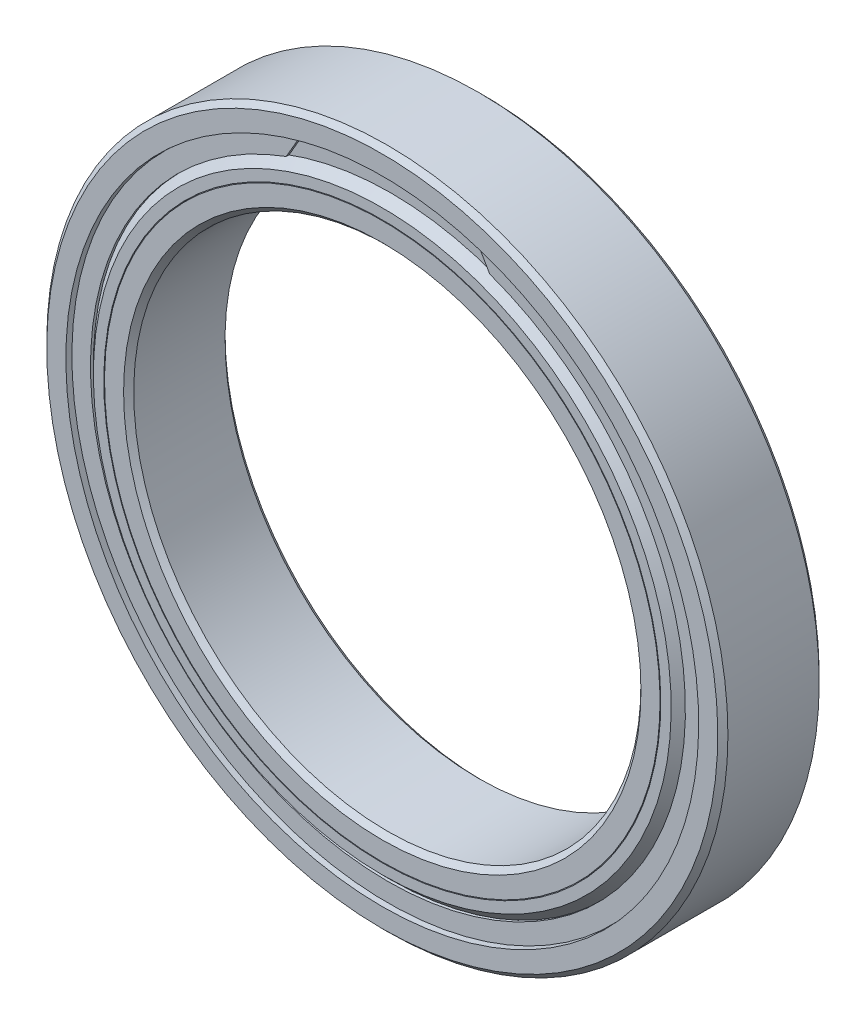
SolidWorks part; units mm, degrees
ref_plane "Front Plane" through (0, 0, 0) normal (0, 0, 1) x (1, 0, 0)
ref_plane "Top Plane" through (0, 0, 0) normal (0, 1, 0) x (1, 0, 0)
ref_plane "Right Plane" through (0, 0, 0) normal (1, 0, 0) x (0, 0, -1)
sketch "Sketch1" plane through (0, 0, 0) normal (0, 0, 1) x (1, 0, 0)
  circle A0 centre (0, 0) radius 23.5
  circle A1 centre (0, 0) radius 17.5
  dimension "OD" = 47
  dimension "ID" = 35
  dimension "For Shaft Diameter" = 35
sketch "Sketch8" plane through (0, 0, 0) normal (1, 0, 0) x (0, 0, -1)
  line L1 (-3.5, 23.5) -> (3.5, 23.5)
  line L2 (-3.5, 23.5) -> (-3.5, -23.5)
  line L3 (-3.5, -23.5) -> (3.5, -23.5)
  line L4 (3.5, 23.5) -> (3.5, -23.5)
  line L5 (-3.5, 23.5) -> (3.5, -23.5) construction
  line L6 (-3.5, -23.5) -> (3.5, 23.5) construction
  point P0 (0, 0)
  point P6 (0, -23.5)
  dimension "Width" = 7
sketch "Sketch5" plane through (0, 0, 0) normal (1, 0, 0) x (0, 0, -1)
  line L0 (-3.5, 0) -> (3.5, 0) construction
  line L1 (0, 23.5) -> (0, -23.5) construction
  line L2 (3.15, 23.5) -> (-3.15, 23.5)
  line L3 (-3.15, 23.5) -> (-3.5, 23.15)
  line L4 (-3.5, 23.15) -> (-3.5, 21.8333)
  line L5 (-3.5, 21.8333) -> (-1.5556, 21.8333)
  line L6 (3.5, 21.8333) -> (1.5556, 21.8333)
  line L7 (3.5, 23.15) -> (3.5, 21.8333)
  line L8 (3.15, 23.5) -> (3.5, 23.15)
  line L9 (0, 23.5) -> (0, 20.5) construction
  line L10 (0, 20.5) -> (0, 17.5) construction
  line L11 (-1.9373, 21.1667) -> (-3.5, 21.1667) construction
  line L12 (2.5281, 20.5254) -> (2.9091, 20.5254)
  line L13 (-2.5281, 20.5254) -> (-2.9091, 20.5254)
  line L14 (-2.5281, 20.5254) -> (-2.5281, 21.8079)
  line L15 (-2.5281, 21.8079) -> (-2.9091, 21.8079)
  line L16 (-2.9091, 20.5254) -> (-2.9091, 21.8079)
  line L17 (-2.5281, 20.5254) -> (-2.9091, 21.8079) construction
  line L18 (-2.5281, 21.8079) -> (-2.9091, 20.5254) construction
  line L19 (2.9091, 20.5254) -> (2.9091, 21.8079)
  line L20 (2.5281, 21.8079) -> (2.9091, 21.8079)
  line L21 (2.5281, 20.5254) -> (2.5281, 21.8079)
  line L22 (0, 23.5) -> (0, -23.5) construction
  line L23 (3.5, 0) -> (3.5, 23.5) construction
  line L24 (3.5, 23.5) -> (3.15, 23.5) construction
  line L25 (-3.5, 0) -> (-3.5, 23.5) construction
  line L26 (-3.5, 23.5) -> (-3.15, 23.5) construction
  line L27 (3.5, 0) -> (3.5, -23.5) construction
  line L28 (-3.5, 0) -> (-3.5, -23.5) construction
  line L29 (-3.5, -23.5) -> (3.5, -23.5) construction
  line L30 (-2.0488, 20.5) -> (-2.0488, 21.8333) construction
  line L31 (-2.0488, 21.1667) -> (-2.0488, 20.5) construction
  line L32 (-2.0488, 20.8333) -> (-2.0488, 21.1667) construction
  arc A0 (-1.5556, 21.8333) -> (1.5556, 21.8333) centre (0, 20.5) cw
  circle A1 centre (0, 20.5) radius 2.0488 construction
  point P14 (0, 17.5)
  point P15 (-2.7186, 21.1667)
  point P36 (-2.0488, 21.1667)
  dimension "D1" = 45
  dimension "D2" = 0.35
  dimension "D3" = 3.1111
  dimension "D4" = 1.3333
  dimension "D5" = 0.381
  dimension "D6" = 0.0254
revolve "Revolve1" add sketch "Sketch5" angle 360 about L0
sketch "Sketch3" plane through (0, 0, 0) normal (1, 0, 0) x (0, 0, -1)
  line L0 (-3.5, 19.1667) -> (-1.5556, 19.1667)
  line L1 (0, 23.5) -> (0, -23.5) construction
  line L2 (-3.5, 23.15) -> (-3.5, 21.8333) construction
  line L3 (-3.5, 19.1667) -> (-3.5, 17.85)
  line L4 (-3.15, 23.5) -> (-3.5, 23.15) construction
  line L5 (-3.5, 17.85) -> (-3.15, 17.5)
  line L6 (-3.15, 17.5) -> (3.15, 17.5)
  line L7 (3.15, 23.5) -> (3.15, -23.5) construction
  line L8 (3.15, 17.5) -> (3.5, 17.85)
  line L9 (3.5, -23.15) -> (3.5, 23.15) construction
  line L10 (3.5, 17.85) -> (3.5, 19.1667)
  line L11 (3.5, 19.1667) -> (1.5556, 19.1667)
  line L13 (3.15, 23.5) -> (3.5, 23.15) construction
  arc A0 (1.5556, 21.8333) -> (-1.5556, 21.8333) centre (0, 20.5) ccw construction
  arc A1 (1.5556, 19.1667) -> (-1.5556, 19.1667) centre (0, 20.5) cw
revolve "Revolve3" add sketch "Sketch3" angle 360 about L0
sketch "Sketch9" plane through (0, 0, 0) normal (1, 0, 0) x (0, 0, -1)
  line L0 (-2.9091, 20.5254) -> (-3.5, 19.9345)
  line L1 (-3.5, 0) -> (-3.5, 23.5) construction
  line L2 (-3.5, 19.9345) -> (-3.5, 19.2167)
  line L3 (-3.5, 19.2167) -> (-2.5281, 19.2167)
  line L4 (-2.5281, 19.2167) -> (-2.5281, 20.5254)
  line L5 (-3.5, 19.1667) -> (-1.5556, 19.1667) construction
  line L6 (-2.9091, 20.5254) -> (-2.5281, 20.5254)
  line L7 (0, 23.5) -> (0, -23.5) construction
  line L8 (0, 23.5) -> (0, -23.5) construction
  line L9 (2.9091, 20.5254) -> (2.5281, 20.5254)
  line L10 (2.5281, 19.2167) -> (2.5281, 20.5254)
  line L11 (3.5, 19.2167) -> (2.5281, 19.2167)
  line L12 (3.5, 19.9345) -> (3.5, 19.2167)
  line L13 (2.9091, 20.5254) -> (3.5, 19.9345)
  dimension "D1" = 0.05
  dimension "D2" = 45
revolve "Revolve5" add sketch "Sketch9" angle 360 about L0
sketch "Sketch10" plane through (0, 0, 2.9091) normal (0, 0, 1) x (1, 0, 0)
  line L0 (0, 0) -> (-7.4588, 20.4928) construction
  line L1 (-7.4588, 20.4928) -> (7.4588, 20.4928) construction
  line L2 (7.4588, 20.4928) -> (0, 0) construction
  line L3 (-7.0201, 19.2876) -> (-6.061, 20.9487)
  line L4 (0, 0) -> (0, 23.5) construction
  line L5 (0, 0) -> (0, 23.5) construction
  line L6 (7.0201, 19.2876) -> (6.061, 20.9487)
  circle A0 centre (0, 0) radius 20.5254 construction
  circle A1 centre (0, 0) radius 21.8079
  circle A2 centre (0, 0) radius 21.8079 construction
  circle A3 centre (0, 0) radius 20.5254 construction
  circle A4 centre (0, 0) radius 21.8079 construction
  arc A7 (-7.0201, 19.2876) -> (7.0201, 19.2876) centre (0, 0) ccw
  arc A8 (6.061, 20.9487) -> (-6.061, 20.9487) centre (0, 0) cw
  dimension "D2" = 40
  dimension "D3" = 30
  dimension "D1" = 0
extrude "Boss-Extrude1" add sketch "Sketch10" along normal blind 0.2 separate body
mirror "Mirror2" about plane through (0, 0, 0) normal (0, 0, 1) of bodies 149
sketch "Sketch4" plane through (0, 0, 0) normal (1, 0, 0) x (0, 0, -1)
  line L0 (-2.0488, 20.5) -> (2.0488, 20.5)
  arc A2 (-2.0488, 20.5) -> (2.0488, 20.5) centre (0, 20.5) cw
  arc A3 (1.5556, 21.8333) -> (-1.5556, 21.8333) centre (0, 20.5) ccw construction
revolve "Revolve4" add sketch "Sketch4" angle 360 about L0
pattern_circular "CirPattern1" count 17 every 21.176 of bodies 104
ref_axis "Center Axis 1" through (0, 0, -3.15) along (0, 0, 1)
equation "\"D2@Sketch5\" = \"Width@Sketch8\" * .05"
equation "\"D3@Sketch5\" = \"Width@Sketch8\" / 2.25"
equation "\"D4@Sketch5\"=((\"OD@Sketch1\"-\"ID@Sketch1\")/2)/4.5"
equation "\"D2@CirPattern1\" = 360/\"Balls@CirPattern1\""
